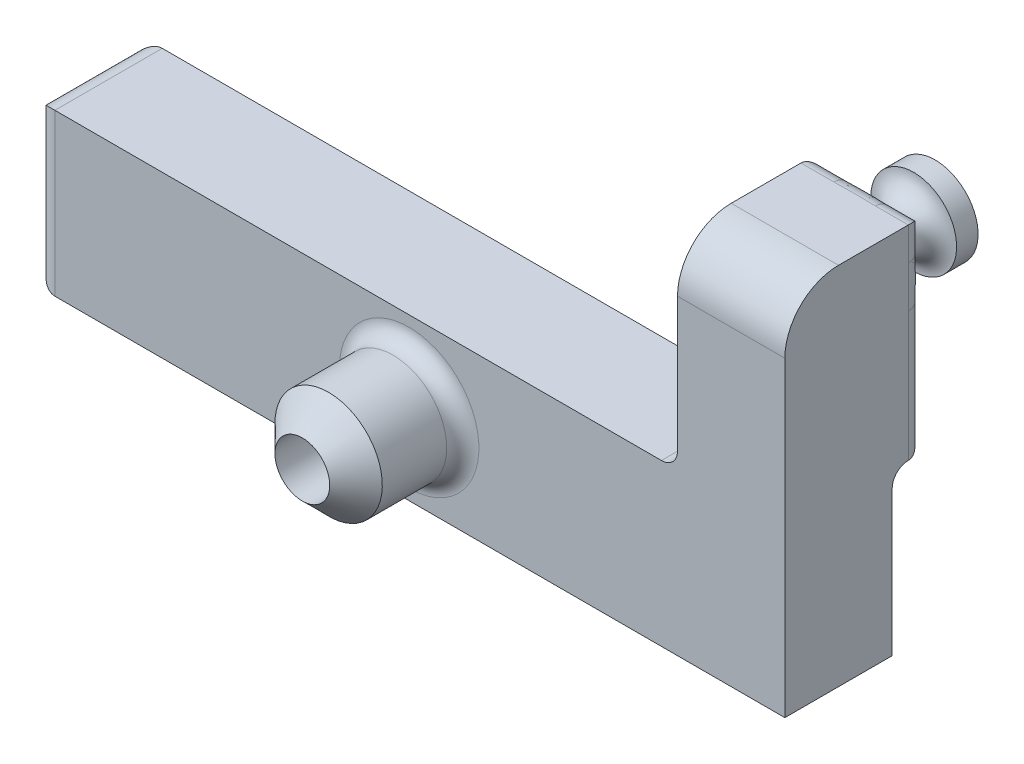
SolidWorks part; units mm, degrees
ref_plane "Front Plane" through (0, 0, 0) normal (0, 0, 1) x (1, 0, 0)
ref_plane "Top Plane" through (0, 0, 0) normal (0, 1, 0) x (1, 0, 0)
ref_plane "Right Plane" through (0, 0, 0) normal (1, 0, 0) x (0, 0, -1)
sketch "Sketch1" plane through (0, 0, 0) normal (0, 0, 1) x (1, 0, 0)
  line L0 (-35, -7.5) -> (35, -7.5)
  line L1 (-35, -7.5) -> (-35, 7.5)
  line L2 (35, -7.5) -> (35, 7.5)
  line L3 (-35, 7.5) -> (35, 7.5)
  line L4 (-35, -7.5) -> (35, 7.5) construction
  line L5 (35, -7.5) -> (-35, 7.5) construction
  circle A0 centre (0, 0) radius 2.55
  point P1 (0, 0)
  dimension "D3" = 5.1
  dimension "D1" = 70
  dimension "D2" = 15
  dimension "D4" = 35
extrude "Boss-Extrude1" add sketch "Sketch1" along normal blind 10
sketch "Sketch5" plane through (0, 0, 0) normal (0, 0, -1) x (-1, 0, 0)
  line L0 (-35, 26.5) -> (-25, 26.5)
  line L1 (-35, 26.5) -> (-35, 7.5)
  line L2 (-25, 26.5) -> (-25, 7.5)
  line L3 (-35, 7.5) -> (-25, 7.5)
  line L7 (-35, 7.5) -> (35, 7.5) construction
  line L8 (-35, -7.5) -> (-35, 7.5) construction
  dimension "D1" = 10
  dimension "D2" = 19
extrude "Boss-Extrude5" add sketch "Sketch5" against normal blind 10 and the other way blind 3 separate body
sketch "Sketch2" plane through (0, 0, 10) normal (0, 0, 1) x (1, 0, 0)
  line L0 (-35, 7.5) -> (-25, 7.5)
  line L1 (-35, 7.5) -> (-35, 17.5)
  line L2 (-25, 7.5) -> (-25, 17.5)
  line L3 (-35, 17.5) -> (-25, 17.5)
  line L4 (35, 7.5) -> (-35, 7.5) construction
  dimension "D1" = 10
  dimension "D2" = 10
extrude "Boss-Extrude2" [suppressed] add sketch "Sketch2" against normal blind 10
sketch "Sketch3" plane through (-35, 0, -3) normal (0, 0, -1) x (-1, 0, 0)
  line L0 (-70, -7.5) -> (-70, 7.5) construction
  line L1 (-60, 7.5) -> (-60, 26.5) construction
  line L2 (-60, 26.5) -> (-70, 26.5) construction
  circle A0 centre (-65, 21.5) radius 2
  point P9 (-60, 17)
  dimension "D1" = 4
  dimension "D2" = 5
  dimension "D3" = 5
fillet "Fillet1" radius 2 4 edges at (-35, 0, 0) (-35, -7.5, 5) (-35, 0, 10) (-35, 7.5, 5)
extrude "Boss-Extrude6" add sketch "Sketch3" along normal blind 4
sketch "Sketch6" plane through (0, 0, -7) normal (0, 0, -1) x (-1, 0, 0)
  circle A2 centre (-30, 21.5) radius 4
  circle A3 centre (-30, 21.5) radius 4
  dimension "D1" = 2
extrude "Boss-Extrude7" add sketch "Sketch6" along normal blind 2
fillet "Fillet4" radius 5 1 edges at (30, 26.5, 10)
combine bodies "Combine1" operation type add bodies to combine 106 105 107 101
fillet "Fillet7" radius 2 2 edges at (28, 21.5, -7) (28, 21.5, -3)
fillet "Fillet3" radius 1.5 5 edges at (30, 7.5, -3) (30, 7.5, 0) (25, 17, -3) (30, 26.5, -3) (35, 17, -3)
fillet "Fillet9" radius 1.5 2 edges at (25, 6.75, 0) (25, 7.5, 5)
sketch "Sketch8" plane through (0, 0, 0) normal (1, 0, 0) x (0, 0, -1)
  line L0 (-10, 0) -> (-20, 0)
  line L1 (-10, 21.5) -> (-10, -7.5) construction
  line L2 (-20, 0) -> (-20, 2.5)
  line L3 (-20, 2.5) -> (-17.5, 5)
  line L4 (-17.5, 5) -> (-10, 5)
  line L5 (-10, 5) -> (-10, 0)
  dimension "D1" = 2.5
  dimension "D2" = 5
  dimension "D3" = 10
  dimension "D4" = 135
revolve "Revolve1" add sketch "Sketch8" angle 360 about L0
sketch "Sketch9" plane through (0, 0, 10) normal (0, 0, -1) x (-1, 0, 0)
  circle A1 centre (0, 0) radius 2.55
  circle A2 centre (0, 0) radius 2.55
  dimension "D1" = 0
extrude "Cut-Extrude1" cut sketch "Sketch9" against normal blind 10
fillet "Fillet10" radius 1.5 1 edges at (0, 5, 10)
